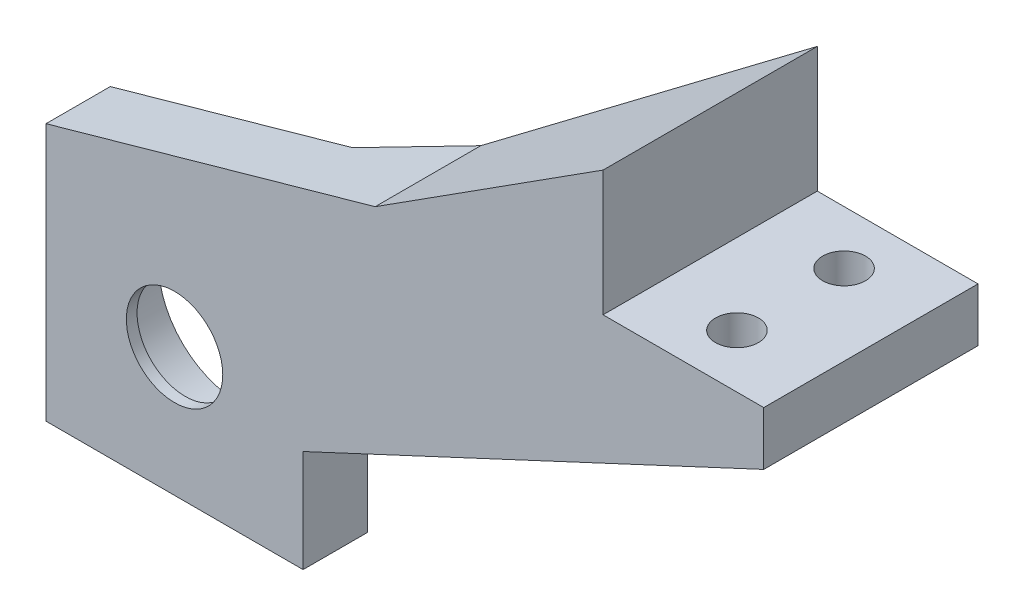
SolidWorks part; units mm, degrees
material "ABS"
ref_plane "Front Plane" through (0, 0, 0) normal (0, 0, 1) x (1, 0, 0)
ref_plane "Top Plane" through (0, 0, 0) normal (0, 1, 0) x (1, 0, 0)
ref_plane "Right Plane" through (0, 0, 0) normal (1, 0, 0) x (0, 0, -1)
sketch "Sketch1" plane through (0, 0, 0) normal (0, 0, 1) x (1, 0, 0)
  circle A0 centre (0, 0) radius 7.5
  circle A1 centre (0, 0) radius 4.5
  circle A2 centre (0, 0) radius 10
  dimension "D1" = 15
  dimension "D2" = 20
  dimension "D3" = 9
extrude "Boss-Extrude1" add sketch "Sketch1" against normal up to surface (5 mm away) contours A2 A0 region at (-9.7172, 0, 0)
extrude "Boss-Extrude2" add sketch "Sketch1<3>" along normal blind 1 contours A0 A1 | A2 A0 region at (-7.2879, 0, 0) region at (-9.7172, 0, 0)
sketch "Sketch1<3>" plane through (0, 0, 0) normal (0, 0, 1) x (1, 0, 0) same geometry as "Sketch1"
sketch "Sketch2" plane through (0, 0, 1) normal (0, 0, 1) x (1, 0, 0)
  line L3 (55, 22.6) -> (40, 22.6)
  line L5 (-12, -0.9326) -> (-12, -12)
  line L6 (-12, -12) -> (12, -12)
  line L8 (40, 22.6) -> (40, 17.6)
  line L13 (40, 17.6) -> (55, 17.6)
  line L14 (55, 17.6) -> (55, 22.6)
  line L15 (-86, 22.6) -> (266, 22.6) construction
  line L16 (10.6203, 22.6) -> (-12, 12.052)
  line L17 (-12, -0.9326) -> (-12, 12.052)
  line L18 (40, 22.6) -> (10.6203, 22.6)
  line L19 (55, 17.6) -> (12, -2.4512)
  line L20 (12, -2.4512) -> (12, -12)
  line L21 (10.6203, 22.6) -> (40, 36.3)
  line L23 (34.0705, 37.9485) -> (-8.8692, 17.9254) construction
  line L24 (40, 22.6) -> (40, 34.3) construction
  line L25 (40, 36.3) -> (40, 22.6)
  circle A1 centre (0, 0) radius 10
  circle A2 centre (0, 0) radius 10 construction
  circle M4 centre (0, 0) radius 10
  dimension "D1" = 12
  dimension "D2" = 24
  dimension "D3" = 15
  dimension "D4" = 5
  dimension "D5" = 25
  dimension "D6" = 4
  dimension "D7" = 12
  dimension "D8" = 2
  dimension "D9" = 0
extrude "Boss-Extrude3" add sketch "Sketch2" against normal up to surface (6 mm away) contours L8 M4 | L6 L5 M4 | L8 | L25 L21 L18 region at (47.5, 20.1, 1) region at (16.0369, 9.9628, 1) region at (30.2068, 27.1667, 1) up to face at (-10, 0, -5)
sketch "Sketch3" plane through (0, 22.6, 0) normal (0, -1, 0) x (1, 0, 0)
  line L0 (40, -286) -> (40, 14) construction
  line L1 (55, -5) -> (40, -5)
  line L2 (55, -5) -> (55, -19)
  line L3 (55, -19) -> (40, -19)
  line L4 (40, -5) -> (40, -19)
  line L5 (55, -5) -> (40, -19) construction
  line L6 (55, -19) -> (40, -5) construction
  line L7 (55, 1) -> (12, 1) construction
  line L8 (40, -19) -> (10.6203, -5)
  line L9 (55, -5) -> (55, 1) construction
  line L10 (40, -5) -> (10.6203, -5)
  line L11 (40, -5) -> (-12, -5) construction
  point P4 (47.5, -12)
  dimension "D1" = 20
  dimension "D2" = 29.3797
extrude "Boss-Extrude7" add sketch "Sketch3" along normal up to surface (11.9946 mm away) contours L4 L10 L8 | L1 L4 L3 L2 region at (47.5, 22.6, -12) region at (30.2068, 22.6, -9.6667) up to face at (33.5, 7.5744, -2)
sketch "Sketch4" plane through (0, 22.6, 0) normal (0, -1, 0) x (1, 0, 0)
  line L1 (55, 1) -> (40, 1)
  line L2 (55, 1) -> (55, -19)
  line L3 (55, -19) -> (40, -19)
  line L4 (40, 1) -> (40, -19)
  line L5 (55, 1) -> (40, -19) construction
  line L6 (55, -19) -> (40, 1) construction
  line L7 (55, -19) -> (55, 1) construction
  line L8 (55, -9) -> (40, -9) construction
  line L9 (47.5, -9.9585) -> (44, -11.9793)
  line L10 (44, -11.9793) -> (44, -16.0207)
  line L11 (44, -16.0207) -> (47.5, -18.0415)
  line L12 (47.5, -18.0415) -> (51, -16.0207)
  line L13 (51, -16.0207) -> (51, -11.9793)
  line L14 (51, -11.9793) -> (47.5, -9.9585)
  line L21 (51, -6.0207) -> (47.5, -8.0415)
  line L22 (51, -1.9793) -> (51, -6.0207)
  line L23 (47.5, 0.0415) -> (51, -1.9793)
  line L24 (44, -1.9793) -> (47.5, 0.0415)
  line L25 (44, -6.0207) -> (44, -1.9793)
  line L26 (47.5, -8.0415) -> (44, -6.0207)
  line L27 (55, 1) -> (40, 1) construction
  circle A0 centre (47.5, -14) radius 3.5 construction
  circle A1 centre (47.5, -4) radius 3.5 construction
  circle A2 centre (47.5, -14) radius 2
  circle A3 centre (47.5, -4) radius 2
  point P4 (47.5, -9)
  point P28 (45.75, -10.9689)
  dimension "D3" = 4
  dimension "D1" = 7.5
  dimension "D2" = 7
  dimension "D4" = 5
  dimension "D5" = 15
  dimension "D6" = 20
extrude "Cut-Extrude4" cut sketch "Sketch4" along normal through all contours A2 | A3 region at (47.5, 22.6, -14) region at (47.5, 22.6, -4)
extrude "Cut-Extrude5" cut sketch "Sketch4<3>" along normal through all from offset 3 contours L26 L21 L22 L23 L24 L25 A3 | L13 L14 L9 L10 L11 L12 A2 region at (49.1965, 22.6, -11.0615) region at (49.1965, 22.6, -6.9385)
sketch "Sketch4<3>" plane through (0, 22.6, 0) normal (0, -1, 0) x (1, 0, 0) same geometry as "Sketch4"
extrude "Boss-Extrude8" add sketch "Sketch3<4>" against normal up to surface (13.7 mm away) contours L4 L10 L8 region at (30.2068, 22.6, -9.6667) up to face at (13.3241, 23.8608, -2.6)
sketch "Sketch3<4>" plane through (0, 22.6, 0) normal (0, -1, 0) x (1, 0, 0) same geometry as "Sketch3"
sketch "Sketch6" plane through (0, 0, 1) normal (0, 0, 1) x (1, 0, 0)
  line L0 (18.7253, 20.7039) -> (40, 34.3)
  line L1 (18.7253, 20.7039) -> (117.3125, 83.7083) construction
  line L2 (40, 36.3) -> (40, 22.6) construction
  line L3 (18.7253, 20.7039) -> (15.9309, 25.0764)
  line L4 (40, 36.3) -> (-12, 12.052) construction
  line L5 (16.9482, 23.4846) -> (18.7253, 20.7039) construction
  line L6 (-12, 12.052) -> (18.7253, 20.7039)
  line L7 (-12, 12.052) -> (40, 36.3)
  line L8 (40, 36.3) -> (40, 34.3)
  line M7 (40, 22.6) -> (40, 36.3)
  line M8 (40, 36.3) -> (-12, 12.052)
extrude "Cut-Extrude6" cut sketch "Sketch6" against normal through all contours L6 L3 M8 | L3 L0 M7 M8 region at (26.7909, 28.0903, 1) region at (7.5521, 19.2774, 1)
